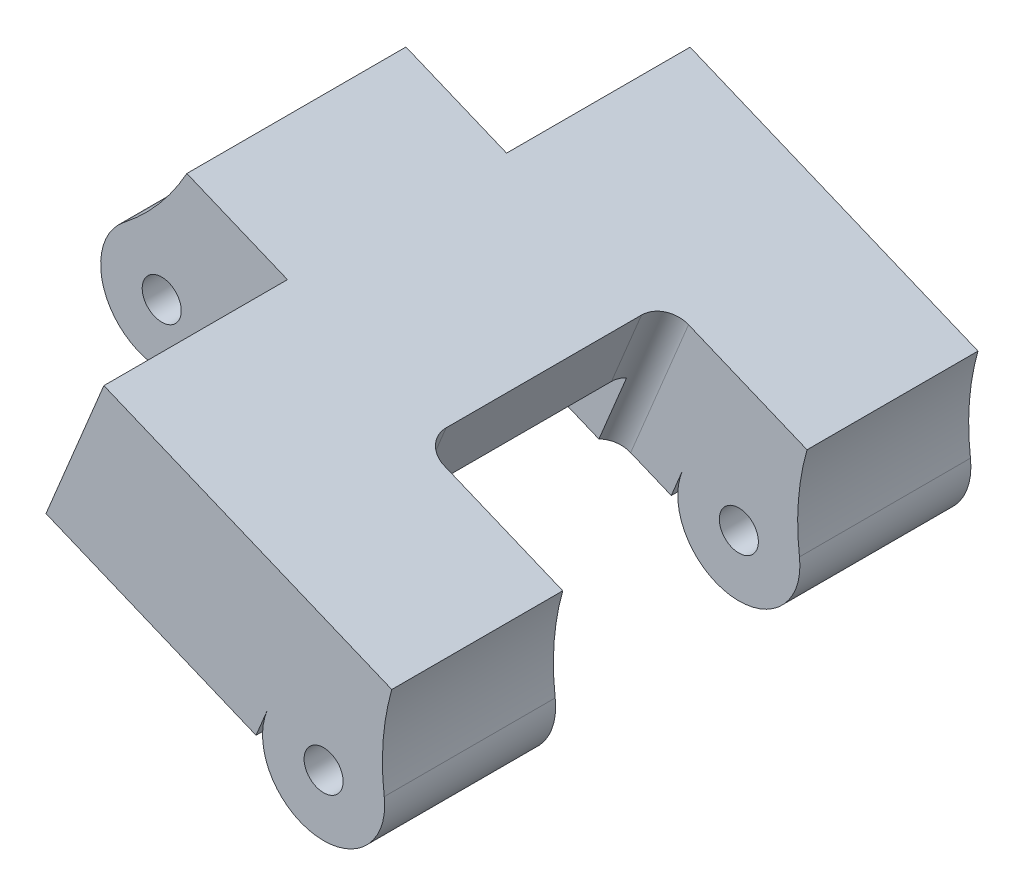
SolidWorks part; units mm, degrees
ref_plane "Alzado" through (0, 0, 0) normal (0, 0, 1) x (1, 0, 0)
ref_plane "Planta" through (0, 0, 0) normal (0, 1, 0) x (1, 0, 0)
ref_plane "Vista lateral" through (0, 0, 0) normal (1, 0, 0) x (0, 0, -1)
sketch "Croquis1" plane through (0, 0, 0) normal (0, 0, 1) x (1, 0, 0)
  line L0 (0, 20) -> (14.1424, 14.1428)
  line L1 (0, 0) -> (0, 22.5)
  line L2 (0, 0) -> (15.9102, 15.9106)
  line L3 (1.0294, 24.9855) -> (16.9334, 18.3988)
  line L4 (0, 22.5) -> (1.0294, 24.9855)
  line L5 (15.905, 15.9158) -> (16.9334, 18.3988)
  circle A0 centre (0, 20) radius 2.5
  circle A1 centre (14.1424, 14.1428) radius 2.5
  arc A2 (-2.7435, 19.8109) -> (2.7435, 19.8109) centre (0, 20) ccw construction
  arc A3 (12.0683, 15.9485) -> (15.9482, 12.0688) centre (14.1424, 14.1428) ccw construction
  arc A4 (16.414, 13.0989) -> (-2.3442, 20.8688) centre (0, 0) ccw
  arc A5 (12.0683, 15.9485) -> (2.7435, 19.8109) centre (0, 0) ccw construction
  circle A6 centre (0, 20) radius 0.8
  circle A8 centre (14.1424, 14.1428) radius 0.8
  dimension "D1" = 5
  dimension "D2" = 5
  dimension "D4" = 1
  dimension "D5" = 1.6
  dimension "D6" = 1.6
  dimension "D3" = 5
extrude "Saliente-Extruir1" add sketch "Croquis1" against normal blind 16 and the other way blind 8 contours A4 A1 L5 L3 L4 A0 | A1 A4 A0 L0 | A6 A4 A0 L1 | A6 L0 A0 A4 | A6 L1 A0 L0 | A6 A4 A0 L1 | A6 L1 A0 A4 | A8 L2 A1 A4 | A8 A4 A1 L0 | A8 L0 A1 L2 | A8 L2 A1 A4 | A8 A4 A1 L2 region at (1.5498, 20.1874, 0) region at (0.9411, 18.5916, 0) region at (-1.2272, 19.3417, 0) region at (7.5183, 18.1516, 0) region at (-0.9403, 21.5934, 0) region at (0.9403, 21.5934, 0) region at (13.1785, 15.371, 0) region at (12.4811, 13.8123, 0) region at (8.4556, 20.4222, 0) region at (14.6039, 15.9343, 0) region at (14.5445, 12.8093, 0) region at (15.9338, 14.6043, 0)
sketch "Croquis3" plane through (8.9835, 21.6913, 0) normal (0.3826, 0.9239, 0) x (0.9239, -0.3826, 0)
  line L0 (-10.1527, 4) -> (10.1546, 4) construction
  line L1 (-10.1527, 16) -> (-10.1527, -8) construction
  line L2 (10.1546, -8) -> (10.1546, 16) construction
  line L3 (-10.1527, -8) -> (-4.1527, -8)
  line L4 (-8.6093, -8) -> (8.6046, -8) construction
  line L5 (-4.1527, -8) -> (-4.1527, -0.4851)
  line L6 (-4.1527, -0.4851) -> (-10.1527, -0.4851)
  line L7 (-10.1527, -0.4851) -> (-10.1527, -8)
  line L8 (-4.1527, 8.4851) -> (-10.1527, 8.4851)
  line L9 (-4.1527, 16) -> (-4.1527, 8.4851)
  line L10 (-10.1527, 16) -> (-4.1527, 16)
  line L11 (-10.1527, 8.4851) -> (-10.1527, 16)
  dimension "D1" = 6
extrude "Cortar-Extruir1" cut sketch "Croquis3" against normal blind 16
sketch "Croquis4" plane through (8.9835, 21.6913, 0) normal (0.3826, 0.9239, 0) x (0.9239, -0.3826, 0)
  line L0 (8.6046, -8) -> (8.6046, 16) construction
  line L1 (2.3546, -1) -> (14.8546, -1)
  line L2 (2.3546, -1) -> (2.3546, 9)
  line L3 (2.3546, 9) -> (14.8546, 9)
  line L4 (14.8546, -1) -> (14.8546, 9)
  line L5 (2.3546, -1) -> (14.8546, 9) construction
  line L6 (2.3546, 9) -> (14.8546, -1) construction
  point P0 (8.6046, 4)
  dimension "D1" = 10
  dimension "D2" = 12.5
extrude "Cortar-Extruir2" cut sketch "Croquis4" against normal blind 16
fillet "Redondeo1" radius 10 3 edges at (15.905, 15.9158, 4.5) (15.905, 15.9158, -12.5) (0, 22.5, -4)
ref_plane "Plano1" through (0, 0, -8.4851) normal (0, 0, -1) x (-1, 0, 0)
sketch "Croquis5" plane through (0, 0, 8) normal (0, 0, 1) x (1, 0, 0)
  line L0 (2.3097, 19.0434) -> (2.8048, 20.2388)
  line L1 (3.2336, 18.6608) -> (2.3097, 19.0434) construction
  line L2 (11.8327, 15.0994) -> (12.3149, 16.2638)
  line L3 (2.3097, 19.0434) -> (11.8327, 15.0994)
  arc A1 (12.3149, 16.2638) -> (2.8048, 20.2388) centre (-0.1726, -0.2485) ccw
  arc A2 (-1.5434, 21.9667) -> (2.3097, 19.0434) centre (0, 20) ccw construction
  arc A3 (11.8327, 15.0994) -> (16.624, 14.4458) centre (14.1424, 14.1428) ccw construction
extrude "Cortar-Extruir3" cut sketch "Croquis5" against normal through all
ref_plane "Plano2" through (5.1468, 23.2803, -16) normal (0.9239, -0.3826, 0) x (0, 0, -1)
sketch "Croquis7" plane through (0, 0, -16) normal (0, 0, -1) x (-1, 0, 0)
  line L0 (-12.3149, 16.2638) -> (-11.8327, 15.0994)
  line L1 (-11.8327, 15.0994) -> (-12.3149, 16.2638) construction
  line L2 (-11.8327, 15.0994) -> (-2.3097, 19.0434)
  line L3 (-2.3097, 19.0434) -> (-2.8048, 20.2388)
  arc A0 (-16.624, 14.4458) -> (-11.8327, 15.0994) centre (-14.1424, 14.1428) ccw construction
  arc A1 (-12.3149, 16.2638) -> (-2.8048, 20.2388) centre (0.1726, -0.2485) cw
extrude "Saliente-Extruir2" add sketch "Croquis7" against normal up to vertex (7 mm away) up to point (9.9296, 17.8219, -9)
sketch "Croquis8" plane through (0, 0, 8) normal (0, 0, 1) x (1, 0, 0)
  line L0 (11.8327, 15.0994) -> (12.3149, 16.2638)
  line L1 (11.8327, 15.0994) -> (12.3149, 16.2638) construction
  line L4 (11.159, 20.7903) -> (9.9296, 17.8219)
  line L5 (2.8048, 20.2388) -> (2.3097, 19.0434)
  line L6 (2.3097, 19.0434) -> (11.8327, 15.0994)
  line L7 (16.9334, 18.3988) -> (11.159, 20.7903)
  line L9 (2.8048, 20.2388) -> (2.3097, 19.0434)
  line L10 (2.3097, 19.0434) -> (11.8327, 15.0994)
  arc A0 (9.9296, 17.8219) -> (12.3149, 16.2638) centre (-0.1726, -0.2485) cw
  arc A4 (9.9296, 17.8219) -> (3.8157, 20.0662) centre (-0.1726, -0.2485) ccw
  arc A5 (3.8157, 20.0662) -> (2.8048, 20.2388) centre (-0.1726, -0.2485) ccw
  arc A6 (11.8327, 15.0994) -> (16.624, 14.4458) centre (14.1424, 14.1428) ccw
  arc A7 (16.9334, 18.3988) -> (16.624, 14.4458) centre (26.5503, 15.6576) ccw
  arc A8 (9.9296, 17.8219) -> (3.8157, 20.0662) centre (-0.1726, -0.2485) ccw
  arc A9 (3.8157, 20.0662) -> (2.8048, 20.2388) centre (-0.1726, -0.2485) ccw
  dimension "D1" = 0
extrude "Saliente-Extruir3" add sketch "Croquis8" against normal up to vertex (7 mm away) up to point (12.3149, 16.2638, 1)
sketch "Croquis9" plane through (0, 0, -16) normal (0, 0, -1) x (-1, 0, 0)
  line L0 (-3.8157, 20.0662) -> (-3.2336, 18.6608)
  line L1 (-3.8157, 20.0662) -> (-5.1468, 23.2803) construction
  line L2 (-11.8327, 15.0994) -> (-2.3097, 19.0434) construction
  line L3 (-3.2336, 18.6608) -> (-2.3097, 19.0434)
  line L4 (-2.3097, 19.0434) -> (-2.8048, 20.2388)
  line L6 (-3.8157, 20.0662) -> (-3.8209, 20.0788)
  line L7 (-3.8209, 20.0788) -> (-2.8048, 20.2522)
  line L8 (-2.8048, 20.2522) -> (-2.8048, 20.2388)
  arc A0 (-2.8048, 20.2388) -> (-3.8157, 20.0662) centre (0.1726, -0.2485) ccw construction
  arc A1 (-2.3097, 19.0434) -> (1.5434, 21.9667) centre (0, 20) ccw construction
extrude "Cortar-Extruir4" cut sketch "Croquis9" against normal through all
sketch "Croquis10" plane through (0, 0, -9) normal (0, 0, 1) x (1, 0, 0)
  line L0 (3.2336, 18.6608) -> (3.8157, 20.0662)
  line L1 (9.9296, 17.8219) -> (9.2458, 16.1708)
  line L2 (11.8327, 15.0994) -> (3.2336, 18.6608) construction
  line L3 (9.2458, 16.1708) -> (3.2336, 18.6608)
  arc A0 (9.9296, 17.8219) -> (3.8157, 20.0662) centre (-0.1726, -0.2485) ccw
extrude "Saliente-Extruir4" add sketch "Croquis10" along normal blind 0.5
sketch "Croquis11" plane through (0, 0, 1) normal (0, 0, -1) x (-1, 0, 0)
  line L0 (-9.9296, 17.8219) -> (-9.2458, 16.1708)
  line L1 (-3.2336, 18.6608) -> (-11.8327, 15.0994) construction
  line L2 (-9.2458, 16.1708) -> (-3.2336, 18.6608)
  line L3 (-3.2336, 18.6608) -> (-3.8157, 20.0662)
  arc A0 (-9.9296, 17.8219) -> (-3.8157, 20.0662) centre (0.1726, -0.2485) cw
extrude "Saliente-Extruir5" add sketch "Croquis11" along normal blind 0.5
fillet "Redondeo2" radius 1 2 edges at (10.2024, 18.4806, -9) (10.2024, 18.4806, 1)
sketch "Croquis12" plane through (0, 0, 8) normal (0, 0, 1) x (1, 0, 0)
  line L0 (11.8327, 15.0994) -> (11.4365, 14.1428)
  line L1 (11.4365, 14.1428) -> (11.3762, 13.9973)
  line L2 (11.3762, 13.9973) -> (2.7772, 17.5587)
  line L3 (3.2336, 18.6608) -> (2.7772, 17.5587)
  line L4 (3.2336, 18.6608) -> (11.8327, 15.0994)
extrude "Saliente-Extruir6" add sketch "Croquis12" against normal up to vertex (7.5 mm away) up to point (9.3696, 16.1195, 0.5)
sketch "Croquis13" plane through (0, 0, -16) normal (0, 0, -1) x (-1, 0, 0)
  line L0 (-3.2336, 18.6608) -> (-2.7772, 17.5587)
  line L1 (-2.7772, 17.5587) -> (-11.3762, 13.9973)
  line L2 (-11.3762, 13.9973) -> (-11.8327, 15.0994)
  line L3 (-11.8327, 15.0994) -> (-3.2336, 18.6608)
extrude "Saliente-Extruir7" add sketch "Croquis13" against normal up to vertex (7.5 mm away) up to point (9.3696, 16.1195, -8.5)
sketch "Croquis15" plane through (8.9835, 21.6913, 0) normal (0.3826, 0.9239, 0) x (0.9239, -0.3826, 0)
  line L0 (8.6046, 9) -> (8.6046, -1)
  line L12 (8.6046, -1) -> (3.3546, -1)
  line L13 (2.3546, 0) -> (2.3546, 8)
  line L14 (3.3546, 9) -> (8.6046, 9)
  line L15 (8.6046, 9) -> (8.6046, 16)
  line L16 (8.6046, 16) -> (-4.1527, 16)
  line L17 (-4.1527, 16) -> (-4.1527, 8.4851)
  line L18 (-4.1527, 8.4851) -> (-8.6093, 8.4851)
  line L19 (-8.6093, 8.4851) -> (-8.6093, -0.4851)
  line L20 (-8.6093, -0.4851) -> (-4.1527, -0.4851)
  line L21 (-4.1527, -0.4851) -> (-4.1527, -8)
  line L22 (-4.1527, -8) -> (8.6046, -8)
  line L23 (8.6046, -8) -> (8.6046, -1)
  line L24 (8.6046, -1) -> (3.3546, -1)
  line L25 (2.3546, 0) -> (2.3546, 8)
  line L26 (3.3546, 9) -> (8.6046, 9)
  arc A2 (2.3546, 0) -> (3.3546, -1) centre (3.3546, 0) ccw
  arc A3 (3.3546, 9) -> (2.3546, 8) centre (3.3546, 8) ccw
  arc A4 (2.3546, 0) -> (3.3546, -1) centre (3.3546, 0) ccw
  arc A5 (3.3546, 9) -> (2.3546, 8) centre (3.3546, 8) ccw
  dimension "D1" = 0
extrude "Cortar-Extruir5" cut sketch "Croquis15" against normal up to vertex (6.1929 mm away) up to point (11.3762, 13.9973, -16)
